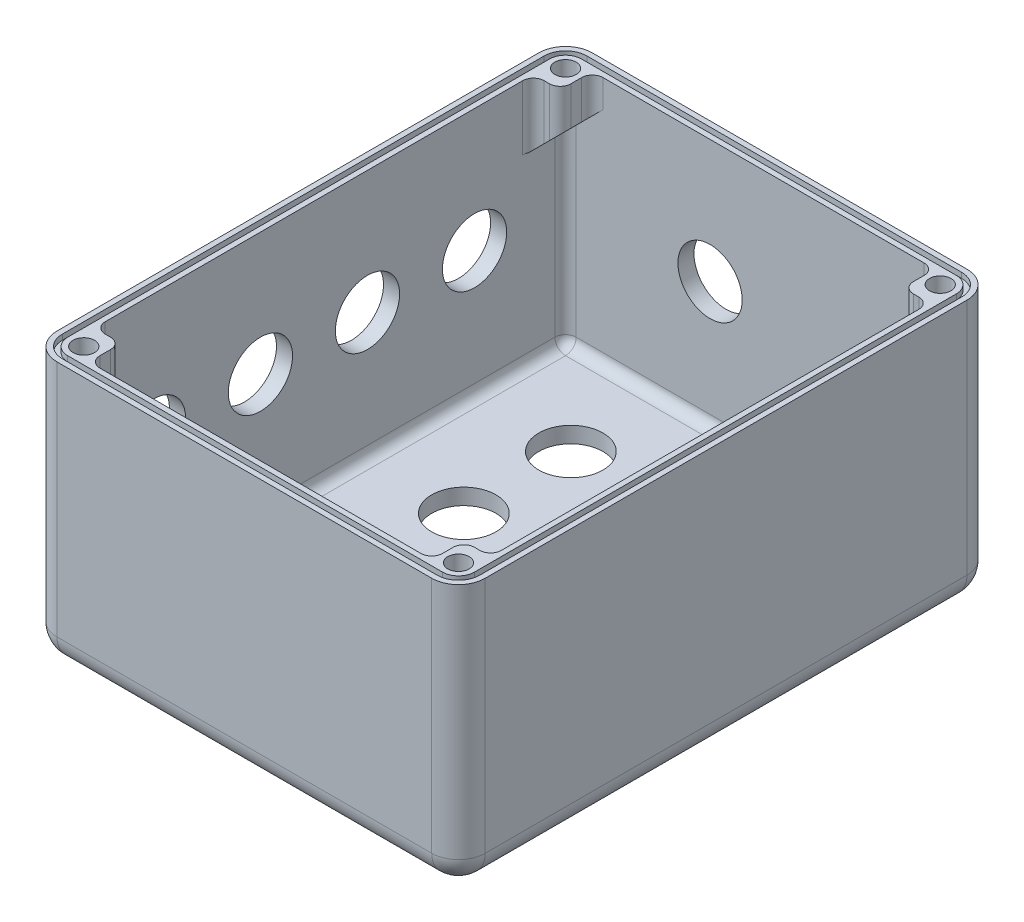
SolidWorks part; units mm, degrees
material "VITON"
ref_plane "Přední" through (0, 0, 0) normal (0, 0, 1) x (1, 0, 0)
ref_plane "Horní" through (0, 0, 0) normal (0, 1, 0) x (1, 0, 0)
ref_plane "Pravá" through (0, 0, 0) normal (1, 0, 0) x (0, 0, -1)
sketch "Skica1" plane through (0, 0, 0) normal (0, 1, 0) x (1, 0, 0)
  line L1 (40, 50) -> (-40, 50)
  line L2 (40, 50) -> (40, -50)
  line L3 (40, -50) -> (-40, -50)
  line L4 (-40, 50) -> (-40, -50)
  line L5 (40, 50) -> (-40, -50) construction
  line L6 (40, -50) -> (-40, 50) construction
  point P0 (0, 0)
  dimension "D1" = 100
  dimension "D2" = 80
extrude "Přidat vysunutím1" add sketch "Skica1" along normal blind 49.5
fillet "Zaoblit1" radius 5 8 edges at (40, 24.75, -50) (40, 0, 0) (40, 24.75, 50) (-40, 24.75, -50) (0, 0, -50) (0, 0, 50) (-40, 24.75, 50) (-40, 0, 0)
shell "Skořepina1" thickness 3 removed face at (0, 49.5, 0)
hole_wizard "Ø12.0 (12) průměr díry1" positions "Skica3" profile "Skica2" hole size "Ø12.0" standard "DIN" end condition through all
sketch "Skica3" plane through (0, 0, 0) normal (0, -1, 0) x (-1, 0, 0)
  point P0 (-1, 30)
  point P3 (-1, 10)
  point P6 (-1, -10)
  point P9 (-1, -30)
  point P12 (19, -30)
  point P15 (19, -10)
  point P18 (19, 10)
  point P21 (19, 30)
sketch "Skica2" plane through (1, 0, -30) normal (1, 0, 0) x (0, 0, -1)
  line L0 (0, 0) -> (0, 49.5)
  line L1 (0, 49.5) -> (6, 49.5)
  line L2 (6, 49.5) -> (6, 0)
  line L5 (6, 0) -> (0, 0)
  line L11 (0, -6.35) -> (0, 107.95) construction
  dimension "Průměr díry skrz" = 12
  dimension "Hloubka díry skrz" = 49.5
sketch "Skica4" plane through (0, 49.5, 0) normal (0, 1, 0) x (1, 0, 0)
  line L32 (-35, -48) -> (35, -48)
  line L33 (38, -45) -> (38, 45)
  line L34 (35, 48) -> (-35, 48)
  line L35 (-38, 45) -> (-38, -45)
  line L36 (-35, -48) -> (35, -48)
  line L37 (38, -45) -> (38, 45)
  line L38 (35, 48) -> (-35, 48)
  line L39 (-38, 45) -> (-38, -45)
  line L60 (35, 49) -> (-35, 49)
  line L61 (-39, 45) -> (-39, -45)
  line L62 (39, -45) -> (39, 45)
  line L63 (-35, -49) -> (35, -49)
  line L64 (35, 49) -> (-35, 49)
  line L65 (-39, 45) -> (-39, -45)
  line L66 (39, -45) -> (39, 45)
  line L67 (-35, -49) -> (35, -49)
  arc A29 (-38, -45) -> (-35, -48) centre (-35, -45) ccw
  arc A30 (35, -48) -> (38, -45) centre (35, -45) ccw
  arc A31 (38, 45) -> (35, 48) centre (35, 45) ccw
  arc A32 (-35, 48) -> (-38, 45) centre (-35, 45) ccw
  arc A33 (-38, -45) -> (-35, -48) centre (-35, -45) ccw
  arc A34 (35, -48) -> (38, -45) centre (35, -45) ccw
  arc A35 (38, 45) -> (35, 48) centre (35, 45) ccw
  arc A36 (-35, 48) -> (-38, 45) centre (-35, 45) ccw
  arc A53 (-35, 49) -> (-39, 45) centre (-35, 45) ccw
  arc A54 (39, 45) -> (35, 49) centre (35, 45) ccw
  arc A55 (-39, -45) -> (-35, -49) centre (-35, -45) ccw
  arc A56 (35, -49) -> (39, -45) centre (35, -45) ccw
  arc A57 (-35, 49) -> (-39, 45) centre (-35, 45) ccw
  arc A58 (39, 45) -> (35, 49) centre (35, 45) ccw
  arc A59 (-39, -45) -> (-35, -49) centre (-35, -45) ccw
  arc A60 (35, -49) -> (39, -45) centre (35, -45) ccw
  dimension "D1" = 1
  dimension "D2" = 1
extrude "Odebrat vysunutím1" cut sketch "Skica4" against normal blind 1
sketch "Skica6" plane through (0, 3, 0) normal (0, 1, 0) x (1, 0, 0)
  line L0 (37, -45) -> (37, 45) construction
  line L1 (37, 33) -> (30, 33)
  line L2 (37, 33) -> (37, 25)
  line L3 (37, 25) -> (30, 25)
  line L4 (30, 33) -> (30, 25)
  line L5 (35, 50) -> (-35, 50) construction
  line L7 (28.2, 33) -> (24.2, 33)
  line L8 (28.2, 33) -> (28.2, 25)
  line L9 (28.2, 25) -> (24.2, 25)
  line L10 (24.2, 33) -> (24.2, 25)
  dimension "D1" = 17
  dimension "D2" = 8
  dimension "D3" = 7
  dimension "D4" = 4
  dimension "D5" = 1.8
extrude "Přidat vysunutím2" add sketch "Skica6" along normal blind 2
sketch "Skica7" plane through (0, 3, 0) normal (0, 1, 0) x (1, 0, 0)
  line L0 (-35, -47) -> (35, -47) construction
  line L1 (28.2, -47) -> (24.2, -47)
  line L2 (28.2, -47) -> (28.2, -45)
  line L3 (28.2, -45) -> (24.2, -45)
  line L4 (24.2, -47) -> (24.2, -45)
  line L5 (37, -45) -> (37, 45) construction
  line L6 (30, -47) -> (37, -47)
  line L7 (30, -47) -> (30, -45)
  line L8 (30, -45) -> (37, -45)
  line L9 (37, -47) -> (37, -45)
  line L10 (30, 33) -> (30, 25) construction
  line L11 (28.2, 25) -> (28.2, 33) construction
  line L12 (24.2, 33) -> (24.2, 25) construction
  dimension "D1" = 2
extrude "Přidat vysunutím3" add sketch "Skica7" along normal blind 42
fillet "Zaoblit2" radius 2 4 edges at (26.2, 3, 45) (32.5, 3, 45) (36.4142, 3.5858, 45) (37, 25, 45)
chamfer "Zkosení1" distance 2 angle 45 1 edges at (24.2, 5, -29)
hole_wizard "Ø12.0 (12) průměr díry2" positions "Skica9" profile "Skica8" hole size "Ø12.0" standard "DIN"
sketch "Skica9" plane through (-40, 0, 0) normal (-1, 0, 0) x (0, 0, 1)
  point P0 (-30, 26.5)
  point P3 (-10, 26.5)
  point P6 (10, 26.5)
  point P9 (30, 26.5)
sketch "Skica8" plane through (-40, 26.5, -30) normal (0, 1, 0) x (0, 0, 1)
  line L0 (0, 0) -> (0, 8.6052)
  line L1 (0, 8.6052) -> (6, 5)
  line L2 (6, 5) -> (6, 0)
  line L5 (6, 0) -> (0, 0)
  line L10 (0, 8.6052) -> (-6, 5) construction
  line L11 (0, -6.35) -> (0, 107.95) construction
  dimension "Průměr díry" = 12
  dimension "Hloubka díry" = 5
  dimension "Úhel vrtání" = 118
hole_wizard "Ø12.0 (12) průměr díry3" positions "Skica11" profile "Skica10" hole size "Ø12.0" standard "DIN"
sketch "Skica11" plane through (0, 0, -50) normal (0, 0, -1) x (-1, 0, 0)
  point P0 (10, 26.5)
sketch "Skica10" plane through (-10, 26.5, -50) normal (1, 0, 0) x (0, 1, 0)
  line L0 (0, 0) -> (0, 8.6052)
  line L1 (0, 8.6052) -> (6, 5)
  line L2 (6, 5) -> (6, 0)
  line L5 (6, 0) -> (0, 0)
  line L10 (0, 8.6052) -> (-6, 5) construction
  line L11 (0, -6.35) -> (0, 107.95) construction
  dimension "Průměr díry" = 12
  dimension "Hloubka díry" = 5
  dimension "Úhel vrtání" = 118
sketch "Skica12" plane through (0, 49.5, 0) normal (0, 1, 0) x (1, 0, 0)
  line L0 (35, 47) -> (-35, 47) construction
  line L1 (32, 47) -> (37, 47)
  line L2 (32, 47) -> (32, 41)
  line L3 (32, 41) -> (37, 41)
  line L4 (37, 47) -> (37, 41)
  line L5 (37, -45) -> (37, 45) construction
  dimension "D1" = 5
  dimension "D2" = 6
extrude "Přidat vysunutím9" add sketch "Skica12" against normal blind 12
hole_wizard "Ø4.0 (4) průměr díry2" positions "Skica16" profile "Skica15" hole size "Ø4.0" standard "DIN"
sketch "Skica16" plane through (0, 49.5, 0) normal (0, 1, 0) x (1, 0, 0)
  point P0 (35, 45)
sketch "Skica15" plane through (35, 49.5, -45) normal (1, 0, 0) x (0, 0, 1)
  line L0 (0, 0) -> (0, 8.2017)
  line L1 (0, 8.2017) -> (2, 7)
  line L2 (2, 7) -> (2, 0)
  line L5 (2, 0) -> (0, 0)
  line L10 (0, 8.2017) -> (-2, 7) construction
  line L11 (0, -6.35) -> (0, 107.95) construction
  dimension "Průměr díry" = 4
  dimension "Hloubka díry" = 7
  dimension "Úhel vrtání" = 118
mirror "Zrcadlit1" about plane through (0, 0, 0) normal (0, 0, 1) of "Přidat vysunutím9", "Ø4.0 (4) průměr díry2"
mirror "Zrcadlit2" about plane through (0, 0, 0) normal (1, 0, 0) of "Zrcadlit1", "Přidat vysunutím9"
chamfer "Zkosení2" distance 4.8 angle 45 4 edges at (-32, 37.5, -44) (32, 37.5, -44) (-32, 37.5, 44) (32, 37.5, 43)
fillet "Zaoblit3" radius 2 12 edges at (32, 45.9, -47) (37, 43.5, -41) (32, 45.9, -41) (-32, 45.9, -47) (-32, 45.9, -41) (-37, 43.5, -41) (-32, 45.9, 47) (-32, 45.9, 41) (-37, 43.5, 41) (37, 43.5, 41) (32, 45.9, 41) (32, 47.25, 47)
